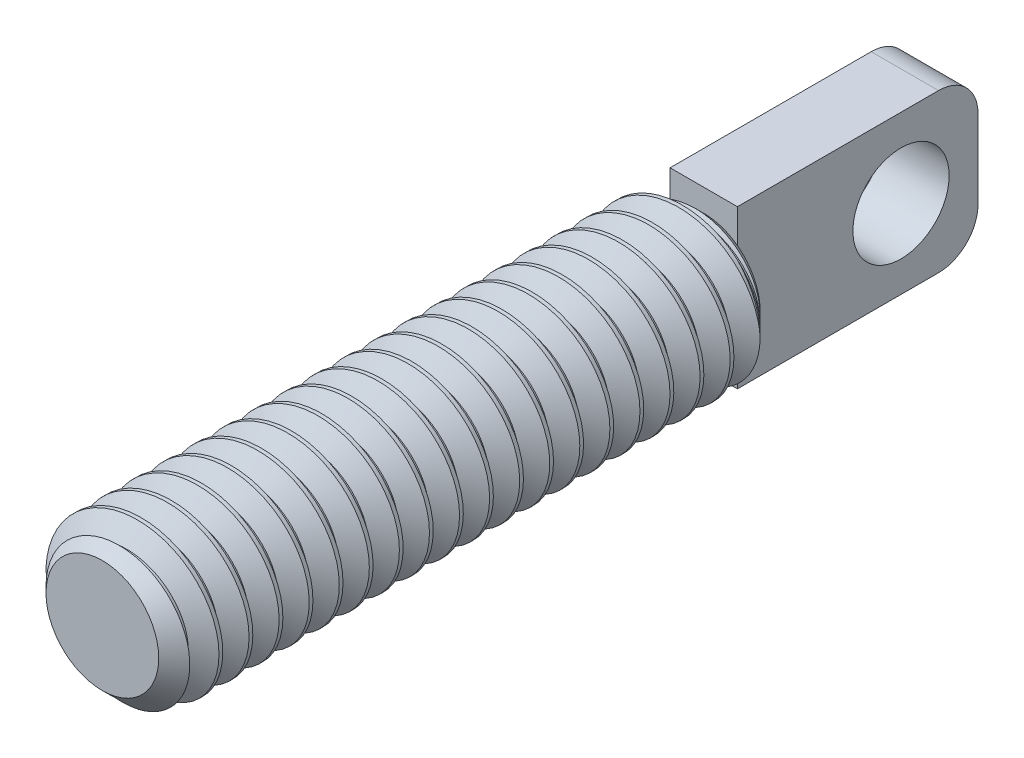
SolidWorks part; units mm, degrees
ref_plane "Front" through (0, 0, 0) normal (0, 0, 1) x (1, 0, 0)
ref_plane "Top" through (0, 0, 0) normal (0, 1, 0) x (1, 0, 0)
ref_plane "Right" through (0, 0, 0) normal (1, 0, 0) x (0, 0, -1)
sketch "Sketch1" plane through (0, 0, 0) normal (0, 0, 1) x (1, 0, 0)
  circle A0 centre (0, 0) radius 2.0828
extrude "Boss-Extrude1" add sketch "Sketch1" along normal mid plane 15.875
sketch "Sketch2" plane through (0, 0, 7.9375) normal (0, 0, 1) x (1, 0, 0)
  circle A1 centre (0, 0) radius 2.0828
  circle A2 centre (0, 0) radius 2.0828
  dimension "D1" = 0
curve "Helix/Spiral1" pitch 0.7937 height 16.6687 turns 21 parameters "Pitch"=0.7937
sketch "Sketch3" plane through (0, 0, 0) normal (1, 0, 0) x (0, 0, -1)
  line L0 (-7.9375, 2.0828) -> (-8.2352, 1.5672)
  line L1 (-8.2352, 1.5672) -> (-8.3344, 1.5672)
  line L2 (-8.3344, 1.5672) -> (-8.632, 2.0828)
  line L3 (-8.632, 2.0828) -> (-7.9375, 2.0828)
  line L4 (-8.0863, 1.825) -> (-8.4832, 1.825) construction
  line L5 (-8.2848, 1.825) -> (-8.2848, 1.5672) construction
  dimension "D1" = 60
  dimension "D2" = 0.0992
  dimension "D3" = 0.3969
chamfer "Chamfer1" distance 0.5953 angle 45 2 edges at (2.0828, 0, -7.9375) (2.0828, 0, 7.9375)
sweep "Cut-Sweep1" cut profiles "Sketch3" path "Helix/Spiral1" align with end faces yes
sketch "Sketch4" plane through (0, 0, 0) normal (1, 0, 0) x (0, 0, -1)
  line L0 (7.9375, -1.4875) -> (7.9375, 1.4875) construction
  line L2 (12.2555, 0) -> (14.2875, 0) construction
  line L3 (14.2875, 1.0414) -> (14.2875, -1.0414)
  line L4 (-7.9375, 1.4875) -> (-7.9375, -1.4875) construction
  line L5 (-8.632, 2.0828) -> (-7.9375, 2.0828) construction
  line L6 (13.2461, 2.0828) -> (7.9375, 2.0828)
  line L7 (7.9375, 2.0828) -> (7.9375, -2.0828)
  line L8 (7.9375, -2.0828) -> (13.2461, -2.0828)
  line L10 (12.2555, 0) -> (7.9375, 0) construction
  circle A0 centre (12.2555, 0) radius 1.27
  arc A1 (14.2875, 1.0414) -> (13.2461, 2.0828) centre (13.2461, 1.0414) ccw
  arc A2 (14.2875, -1.0414) -> (13.2461, -2.0828) centre (13.2461, -1.0414) cw
  point P20 (14.2875, 2.0828)
  dimension "D3" = 1.0414
extrude "Boss-Extrude2" add sketch "Sketch4" along normal mid plane 1.778
equation "\"D3@Helix/Spiral1\" = \"ThreadLength@Boss-Extrude1\"+\"Pitch@Helix/Spiral1\""
equation "\"D2@Sketch3\" = \"Pitch@Helix/Spiral1\"*.125"
equation "\"D3@Sketch3\" = \"Pitch@Helix/Spiral1\"*.5"
equation "\"D1@Chamfer1\" = \"Pitch@Helix/Spiral1\"*.75"
equation "\"D3@Sketch4\" = \"ThreadOD@Sketch1\"*.25"
